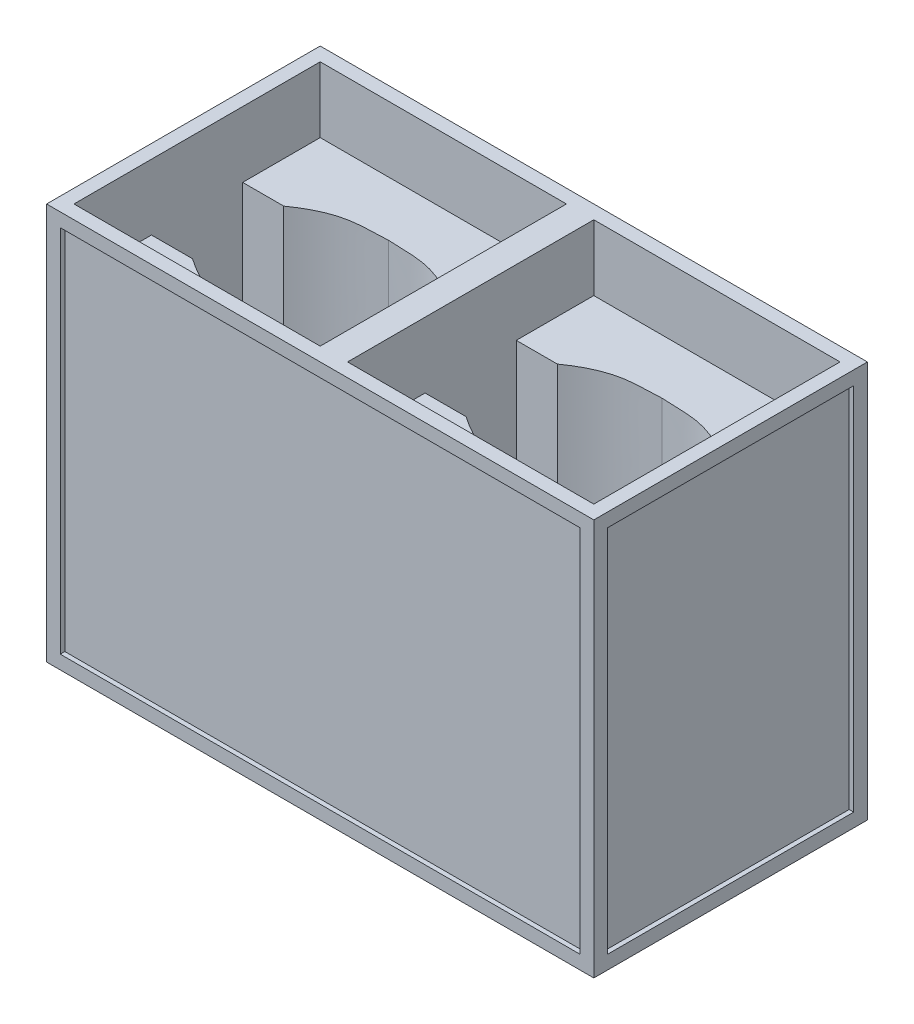
SolidWorks part; units mm, degrees
ref_plane "Front Plane" through (0, 0, 0) normal (0, 0, 1) x (1, 0, 0)
ref_plane "Top Plane" through (0, 0, 0) normal (0, 1, 0) x (1, 0, 0)
ref_plane "Right Plane" through (0, 0, 0) normal (1, 0, 0) x (0, 0, -1)
sketch "Sketch1" plane through (0, 0, 0) normal (0, 1, 0) x (1, 0, 0)
  line L1 (0, 0) -> (120, 0)
  line L2 (0, 0) -> (0, 60)
  line L3 (0, 60) -> (120, 60)
  line L4 (120, 0) -> (120, 60)
extrude "Boss-Extrude1" add sketch "Sketch1" along normal blind 87
sketch "Sketch2" plane through (0, 87, 0) normal (0, 1, 0) x (1, 0, 0)
  line L0 (0, 60) -> (3, 60)
  line L1 (120, 60) -> (0, 60) construction
  line L2 (3, 60) -> (3, 57)
  line L3 (60, 60) -> (60, 0)
  line L4 (0, 0) -> (120, 0) construction
  line L5 (3, 57) -> (57, 57)
  line L6 (57, 57) -> (57, 3)
  line L7 (57, 3) -> (3, 3)
  line L8 (3, 3) -> (3, 57)
  line L9 (117, 3) -> (117, 57)
  line L10 (63, 3) -> (117, 3)
  line L11 (63, 57) -> (63, 3)
  line L12 (117, 57) -> (63, 57)
extrude "Cut-Extrude1" cut sketch "Sketch2" against normal blind 84 contours L8 L7 L6 L5 | L9 L12 L11 L10 region at (30, 87, -30) region at (90, 87, -30)
sketch "Sketch3" plane through (0, 3, 0) normal (0, 1, 0) x (1, 0, 0)
  line L0 (3, 57) -> (57, 3)
  line L1 (30, 30) -> (48, 30)
  line L2 (48, 20) -> (48, 40)
  line L3 (30, 15) -> (30, 45)
  line L4 (48, 40) -> (57, 40)
  line L5 (57, 57) -> (57, 3) construction
  line L6 (57, 40) -> (57, 57)
  line L7 (57, 57) -> (30, 57)
  line L8 (3, 57) -> (57, 57) construction
  line L9 (30, 57) -> (30, 30)
  line L10 (57, 30) -> (48, 30)
  line L11 (12, 20) -> (12, 40)
  line L12 (57, 40) -> (3, 40)
  line L13 (3, 3) -> (3, 57) construction
  line L14 (3, 40) -> (3, 20)
  line L15 (3, 20) -> (57, 20)
  line L16 (57, 57) -> (63, 57)
  line L17 (63, 57) -> (60, 57)
  line L18 (60, 57) -> (60, 51.7728)
  line L19 (117, 20) -> (63, 20)
  line L20 (117, 40) -> (117, 20)
  line L21 (63, 40) -> (117, 40)
  line L22 (108, 20) -> (108, 40)
  line L23 (63, 30) -> (72, 30)
  line L24 (90, 57) -> (90, 30)
  line L25 (63, 57) -> (90, 57)
  line L26 (63, 40) -> (63, 57)
  line L27 (72, 40) -> (63, 40)
  line L28 (90, 15) -> (90, 45)
  line L29 (72, 20) -> (72, 40)
  line L30 (90, 30) -> (72, 30)
  line L31 (117, 57) -> (63, 3)
  line L33 (117, 57) -> (63, 57)
  line L34 (117, 57) -> (117, 3)
  line L35 (117, 3) -> (63, 3)
  line L36 (63, 57) -> (63, 3)
  spline S0 degree 3 poles (30, 45) (33.0237, 44.8539) (39.4181, 44.9718) (44.9583, 42.1387) (48, 40) knots 0 0 0 0 0.455366 1 1 1 1
  spline S1 degree 3 poles (30, 45) (26.9763, 44.8539) (20.5819, 44.9718) (15.0417, 42.1387) (12, 40) knots 0 0 0 0 0.455366 1 1 1 1
  spline S2 degree 3 poles (30, 15) (26.9763, 15.1461) (20.5819, 15.0282) (15.0417, 17.8613) (12, 20) knots 0 0 0 0 0.455366 1 1 1 1
  spline S3 degree 3 poles (30, 15) (33.0237, 15.1461) (39.4181, 15.0282) (44.9583, 17.8613) (48, 20) knots 0 0 0 0 0.455366 1 1 1 1
  spline S4 degree 3 poles (90, 15) (86.9763, 15.1461) (80.5819, 15.0282) (75.0417, 17.8613) (72, 20) knots 0 0 0 0 0.455366 1 1 1 1
  spline S5 degree 3 poles (90, 15) (93.0237, 15.1461) (99.4181, 15.0282) (104.9583, 17.8613) (108, 20) knots 0 0 0 0 0.455366 1 1 1 1
  spline S6 degree 3 poles (90, 45) (93.0237, 44.8539) (99.4181, 44.9718) (104.9583, 42.1387) (108, 40) knots 0 0 0 0 0.455366 1 1 1 1
  spline S7 degree 3 poles (90, 45) (86.9763, 44.8539) (80.5819, 44.9718) (75.0417, 42.1387) (72, 40) knots 0 0 0 0 0.455366 1 1 1 1
  point P26 (12, 30)
  point P55 (108, 30)
  line M6 (3, 57) -> (3, 3)
  line M7 (3, 3) -> (57, 3)
  line M8 (57, 3) -> (57, 57)
  line M9 (57, 57) -> (3, 57)
extrude "Boss-Extrude2" add sketch "Sketch3" along normal blind 69.6 contours S1 L0 L12 M6 | S1 L9 L0 M9 | L9 S0 L4 M8 M9 | S3 L0 L15 M8 | S3 S2 L15 L0 M6 M7 | L31 S4 L19 L36 | S5 S4 L31 L35 L34 L19 | S7 L24 L25 L26 L21 | L24 S6 L31 L33 | L31 S6 L21 L34 region at (19.2158, 3, -51.314) region at (7.9574, 3, -46.1012) region at (75.4349, 3, -49.5634) region at (44.5651, 3, -49.5633) region at (25.5518, 3, -9.738) region at (52.0426, 3, -13.8988) region at (100.7842, 3, -51.3139) region at (112.0426, 3, -46.1012) region at (67.9574, 3, -13.8988) region at (94.4482, 3, -9.738)
sketch "Sketch6" plane through (0, 0, 0) normal (0, -1, 0) x (1, 0, 0)
  line L0 (120, -60) -> (111, -60)
  line L1 (120, -60) -> (0, -60) construction
  line L2 (111, -60) -> (111, -51)
  line L3 (60, -60) -> (60, -47.6916)
  line L4 (120, -30) -> (70.7725, -30)
  line L5 (120, 0) -> (120, -60) construction
  line L6 (60, 0) -> (60, -12.3084)
  line L7 (111, 0) -> (111, -9)
  line L8 (120, 0) -> (111, 0)
  circle A0 centre (111, -51) radius 5.05
  circle A1 centre (9, -51) radius 5.05
  circle A2 centre (9, -9) radius 5.05
  circle A3 centre (111, -9) radius 5.05
extrude "Cut-Extrude2" cut sketch "Sketch6" against normal blind 4 contours A0 | A1 | A2 | A3 region at (114.4699, 0, -54.4699) region at (9, 0, -51) region at (9, 0, -9) region at (107.5301, 0, -12.4699)
sketch "Sketch7" plane through (0, 0, 0) normal (0, 0, 1) x (1, 0, 0)
  line L0 (0, 87) -> (3, 87)
  line L1 (0, 87) -> (120, 87) construction
  line L2 (3, 87) -> (3, 84)
  line L3 (3, 84) -> (117, 84)
  line L4 (117, 84) -> (117, 3)
  line L5 (117, 3) -> (3, 3)
  line L6 (3, 3) -> (3, 84)
extrude "Cut-Extrude3" cut sketch "Sketch7" against normal blind 1 contours L6 L5 L4 L3 | L3 L4 L5 L6 region at (60, 43.5, 0)
sketch "Sketch8" plane through (0, 0, -60) normal (0, 0, -1) x (-1, 0, 0)
  line L0 (-120, 87) -> (-117, 87)
  line L1 (-120, 87) -> (0, 87) construction
  line L2 (-117, 87) -> (-117, 84)
  line L3 (-117, 84) -> (-3, 84)
  line L4 (-3, 84) -> (-3, 3)
  line L5 (-3, 3) -> (-117, 3)
  line L6 (-117, 3) -> (-117, 83.764)
  line L8 (-3, 3) -> (-117, 3)
  line L9 (-3, 3) -> (-3, 84)
  line L10 (-3, 84) -> (-117, 84)
  line L11 (-117, 3) -> (-117, 84)
extrude "Cut-Extrude4" cut sketch "Sketch8" against normal blind 1 contours L11 L6 L5 L4 L3 region at (60, 43.5, -60)
sketch "Sketch9" plane through (0, 0, 0) normal (-1, 0, 0) x (0, 0, 1)
  line L0 (-60, 87) -> (-57, 87)
  line L1 (-60, 87) -> (0, 87) construction
  line L2 (-57, 87) -> (-57, 84)
  line L3 (-57, 84) -> (-3, 84)
  line L4 (-3, 84) -> (-3, 3)
  line L5 (-3, 3) -> (-57, 3)
  line L6 (-57, 3) -> (-57, 84)
extrude "Cut-Extrude5" cut sketch "Sketch9" against normal blind 1 contours L6 L5 L4 L3 region at (0, 43.5, -30)
sketch "Sketch10" plane through (120, 0, 0) normal (1, 0, 0) x (0, 0, -1)
  line L1 (60, 87) -> (57, 87)
  line L2 (60, 87) -> (60, 84)
  line L3 (60, 84) -> (57, 84)
  line L4 (57, 87) -> (57, 84)
  line L5 (57, 84) -> (3, 84)
  line L6 (57, 84) -> (57, 3)
  line L7 (57, 3) -> (3, 3)
  line L8 (3, 84) -> (3, 3)
  line M7 (0, 0) -> (60, 0)
extrude "Cut-Extrude6" cut sketch "Sketch10" against normal blind 1 contours L5 L8 L6 M7 region at (120, 43.5, -30)
